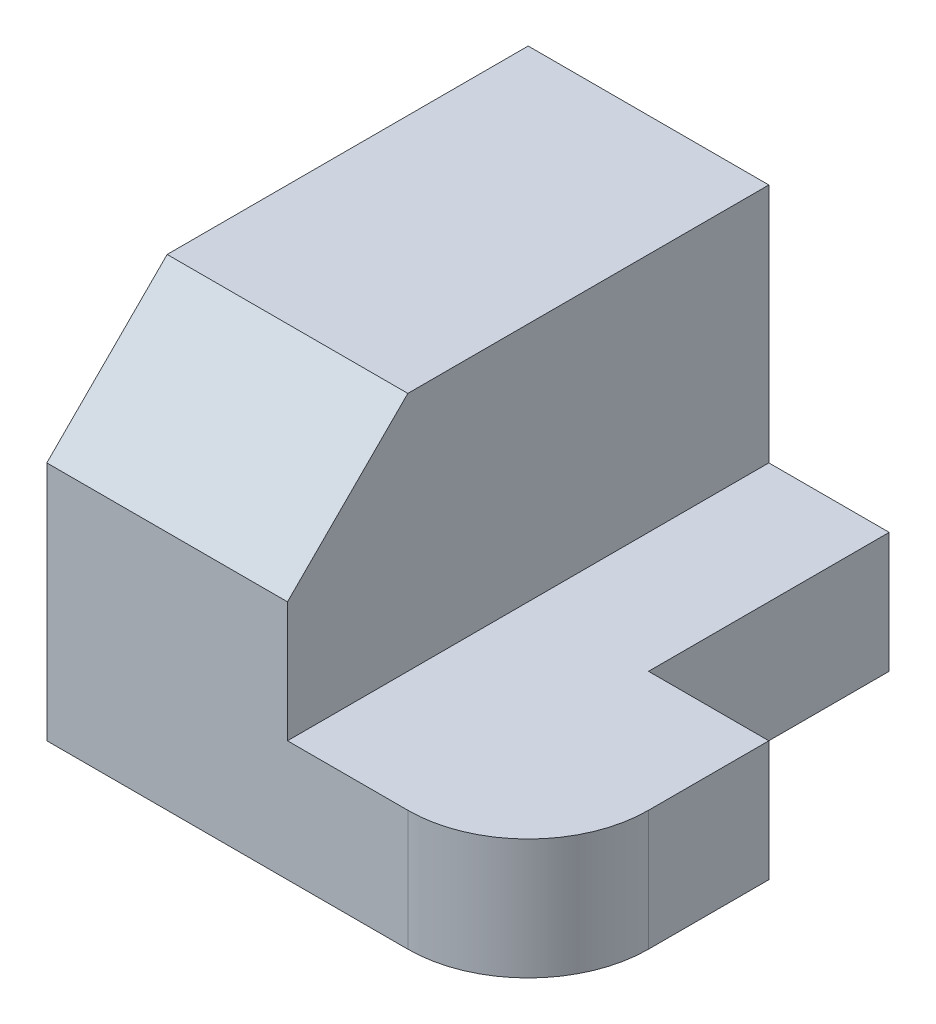
SolidWorks part; units mm, degrees
ref_plane "前基準面" through (0, 0, 0) normal (0, 0, 1) x (1, 0, 0)
ref_plane "上基準面" through (0, 0, 0) normal (0, 1, 0) x (1, 0, 0)
ref_plane "右基準面" through (0, 0, 0) normal (1, 0, 0) x (0, 0, -1)
sketch "草圖1" plane through (0, 0, 0) normal (0, 1, 0) x (1, 0, 0)
  line L1 (5, 10) -> (-5, 10)
  line L2 (5, 10) -> (5, -10)
  line L3 (5, -10) -> (-5, -10)
  line L4 (-5, 10) -> (-5, -10)
  line L5 (5, 10) -> (-5, -10) construction
  line L6 (5, -10) -> (-5, 10) construction
  line L7 (5, 10) -> (10, 10)
  line L8 (5, 10) -> (5, -10)
  line L9 (5, -10) -> (10, -10)
  line L10 (15, 0) -> (15, -5)
  line L13 (15, 0) -> (10, 0)
  line L14 (10, 10) -> (10, 0)
  line L15 (5, -10) -> (-5, -10)
  line L16 (5, -10) -> (5, -5)
  line L17 (5, -5) -> (-5, -5)
  line L18 (-5, -10) -> (-5, -5)
  arc A0 (15, -5) -> (10, -10) centre (10, -5) cw
  point P0 (0, 0)
  dimension "D7" = 5
  dimension "D1" = 20
  dimension "D2" = 10
  dimension "D3" = 10
  dimension "D4" = 5
  dimension "D5" = 10
  dimension "D6" = 5
extrude "填料-伸長1" add sketch "草圖1" along normal blind 5 contours A0 L10 L13 L14 L7 L2 L8 L9 region at (8.9917, 0, 1.399)
extrude "填料-伸長2" add sketch "草圖1<3>" along normal blind 15 contours L17 L2 L1 L4 | L8 L17 L4 L3 region at (0, 0, -2.5) region at (0, 0, 7.5)
sketch "草圖1<3>" plane through (0, 0, 0) normal (0, 1, 0) x (1, 0, 0) same geometry as "草圖1"
sketch "草圖2" plane through (-5, 0, 0) normal (-1, 0, 0) x (0, 0, 1)
  line L0 (5, 15) -> (10, 10)
  line L1 (-10, 15) -> (10, 15) construction
  line L2 (10, 15) -> (10, 0) construction
  line L3 (10, 10) -> (10, 15)
  line L4 (10, 15) -> (5, 15)
  dimension "D1" = 5
  dimension "D2" = 5
extrude "除料-伸長1" cut sketch "草圖2" against normal blind 15
